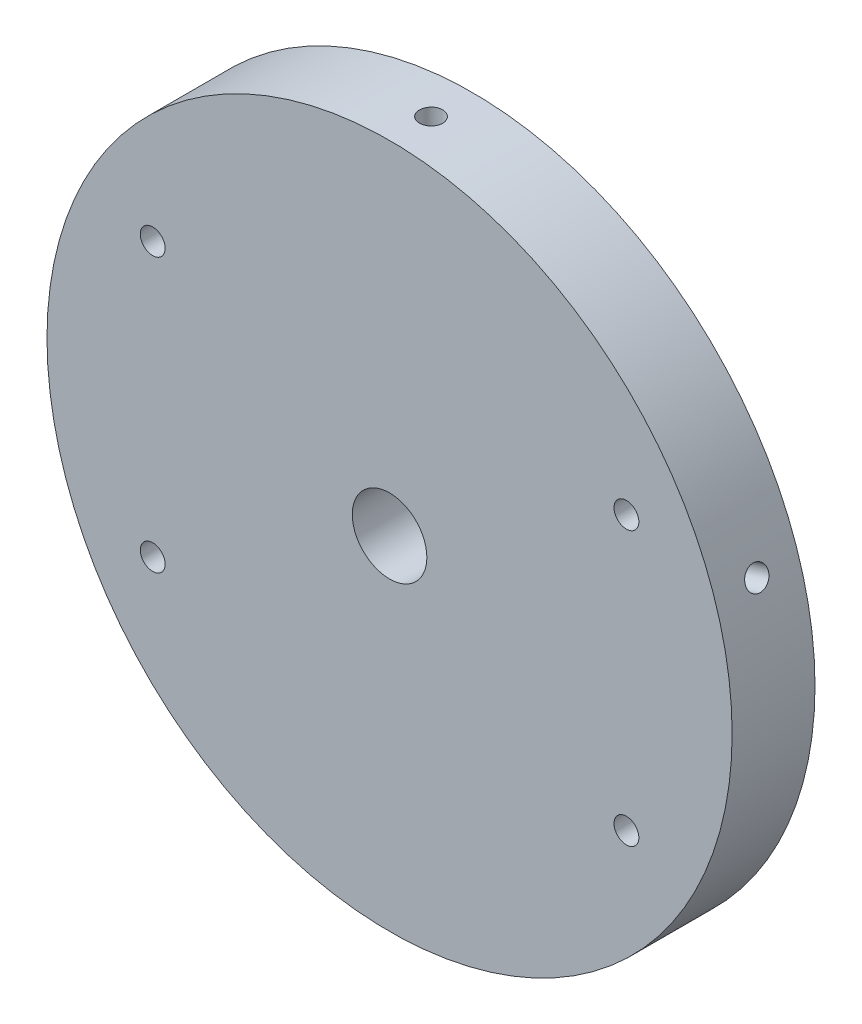
SolidWorks part; units mm, degrees
material "Polyetheretherketone (PEEK)"
ref_plane "Front Plane" through (0, 0, 0) normal (0, 0, 1) x (1, 0, 0)
ref_plane "Top Plane" through (0, 0, 0) normal (0, 1, 0) x (1, 0, 0)
ref_plane "Right Plane" through (0, 0, 0) normal (1, 0, 0) x (0, 0, -1)
sketch "Sketch1" plane through (0, 0, 0) normal (0, 0, 1) x (1, 0, 0)
  circle A0 centre (0, 0) radius 62
  point P3 (0, 0)
  dimension "D1" = 124
extrude "Boss-Extrude1" add sketch "Sketch1" along normal blind 15 contours A0
sketch "Sketch7" plane through (0, 0, 0) normal (0, 0, -1) x (-1, 0, 0)
  line L0 (0, 0) -> (-42.8683, 24.75) construction
  line L2 (0, 0) -> (-42.8683, -24.75) construction
  line L3 (-42.8683, -24.75) -> (-42.8683, 24.75) construction
  line L5 (0, 16.1699) -> (0, -16.1699) construction
  point P0 (-42.8683, 24.75)
  point P2 (-42.8683, -24.75)
  point P20 (42.8683, -24.75)
  point P21 (42.8683, 24.75)
  dimension "D1" = 49.5
  dimension "D2" = 49.5
hole_wizard "M4 Clearance Hole1" positions "Sketch7" profile "Sketch8" hole size "M4" standard "ISO" end condition up to next
sketch "Sketch8" plane through (42.8683, 24.75, 0) normal (1, 0, 0) x (0, 1, 0)
  line L0 (0, 0) -> (0, 15)
  line L1 (0, 15) -> (2.25, 15)
  line L2 (2.25, 15) -> (2.25, 0)
  line L5 (2.25, 0) -> (0, 0)
  line L11 (0, -6.35) -> (0, 107.95) construction
  dimension "Thru Hole Dia." = 4.5
  dimension "Thru Hole Depth" = 15
sketch "Sketch9" plane through (0, 0, 0) normal (0, 0, -1) x (-1, 0, 0)
  point P0 (0, 0)
hole_wizard "M12 Clearance Hole1" positions "Sketch9" profile "Sketch10" hole size "M12" standard "ISO" end condition up to next
sketch "Sketch10" plane through (0, 0, 0) normal (1, 0, 0) x (0, 1, 0)
  line L0 (0, 0) -> (0, 15)
  line L1 (0, 15) -> (6.75, 15)
  line L2 (6.75, 15) -> (6.75, 0)
  line L5 (6.75, 0) -> (0, 0)
  line L11 (0, -6.35) -> (0, 107.95) construction
  dimension "Thru Hole Dia." = 13.5
  dimension "Thru Hole Depth" = 15
hole_wizard "M5 Tapped Hole1" positions "3DSketch1" profile "Sketch11" tap size "M5" standard "ISO"
sketch3d "3DSketch1"
  line L1 (0, 62, 7.5) -> (-58.9655, 19.1591, 7.5) construction
  line L2 (-58.9655, 19.1591, 7.5) -> (-36.4427, -50.1591, 7.5) construction
  line L3 (-36.4427, -50.1591, 7.5) -> (36.4427, -50.1591, 7.5) construction
  line L4 (36.4427, -50.1591, 7.5) -> (58.9655, 19.1591, 7.5) construction
  line L5 (58.9655, 19.1591, 7.5) -> (0, 62, 7.5) construction
  circle A0 centre (0, 0, 7.5) radius 62 construction
  circle A1 centre (0, 0, 0) radius 62 construction
  point P0 (0, 62, 7.5)
  point P2 (58.9655, 19.1591, 7.5)
  point P4 (36.4427, -50.1591, 7.5)
  point P6 (-36.4427, -50.1591, 7.5)
  point P8 (-58.9655, 19.1591, 7.5)
  point P13 (0, 0, 69.5)
  point P19 (0, 0, 62)
  point P28 (0, 0, 0)
  point P29 (0, 0, 0)
  point P30 (0, 0, 0)
  point P31 (0, 0, 0)
  point P32 (0, 0, 0)
  point P33 (0, 0, 0)
  point P34 (0, 0, 0)
  point P35 (0, 0, 0)
  dimension "D1" = 7.5
sketch "Sketch11" plane through (0, 62, 7.5) normal (1, 0, 0) x (0, 0, 1)
  line L0 (0, 0) -> (0, 13.6618)
  line L1 (0, 13.6618) -> (2.1, 12.4)
  line L2 (2.1, 12.4) -> (2.1, 0)
  line L5 (2.1, 0) -> (0, 0)
  line L10 (0, 13.6618) -> (-2.1, 12.4) construction
  line L11 (0, -6.35) -> (0, 107.95) construction
  dimension "Tap Drill Dia." = 4.2
  dimension "Tap Drill Depth" = 12.4
  dimension "Drill Angle" = 118
cosmetic thread "Hole Thread1" parameters "D1"=10, "D2"=5
cosmetic thread "Hole Thread2" parameters "D1"=10, "D2"=5
cosmetic thread "Hole Thread3" parameters "D1"=10, "D2"=5
cosmetic thread "Hole Thread4" parameters "D1"=10, "D2"=5
cosmetic thread "Hole Thread5" parameters "D1"=10, "D2"=5
